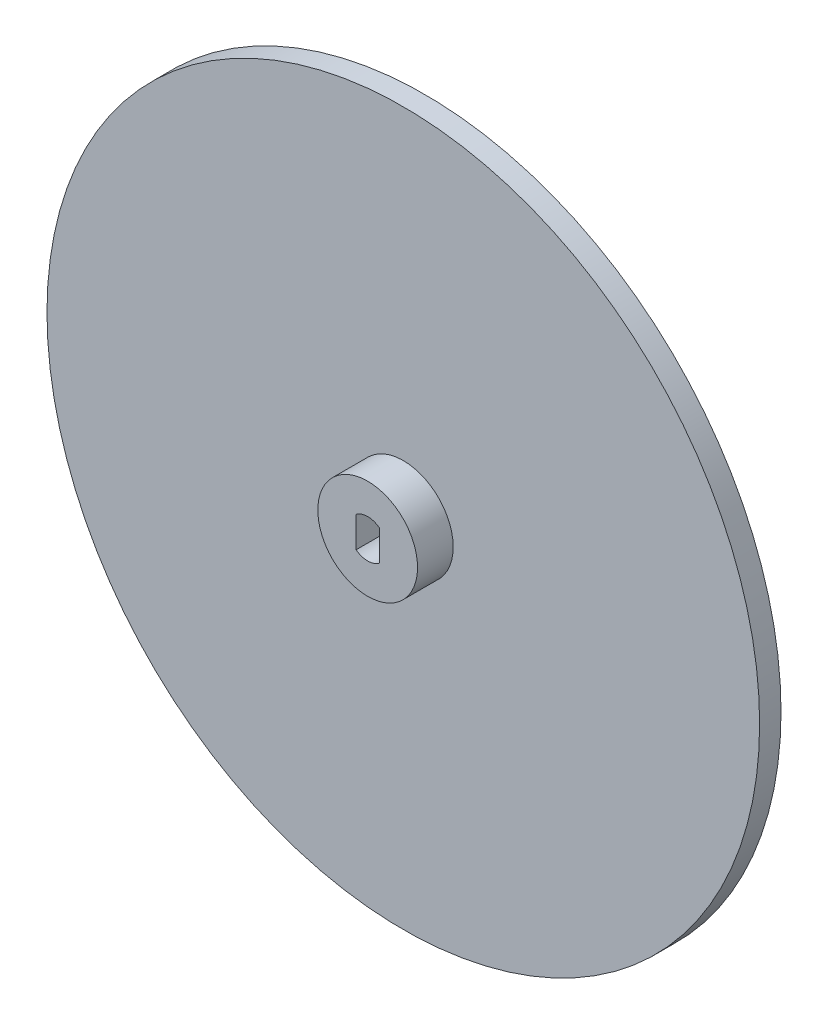
SolidWorks part; units mm, degrees
ref_plane "Front Plane" through (0, 0, 0) normal (0, 0, 1) x (1, 0, 0)
ref_plane "Top Plane" through (0, 0, 0) normal (0, 1, 0) x (1, 0, 0)
ref_plane "Right Plane" through (0, 0, 0) normal (1, 0, 0) x (0, 0, -1)
sketch "Sketch1" plane through (0, 0, 0) normal (0, 0, 1) x (1, 0, 0)
  circle A0 centre (0, 0) radius 50
  dimension "D1" = 100
extrude "Boss-Extrude1" add sketch "Sketch1" against normal blind 3
sketch "Sketch2" plane through (0, 0, 0) normal (0, 0, 1) x (1, 0, 0)
  circle A0 centre (0, 0) radius 7
  dimension "D1" = 14
extrude "Boss-Extrude2" add sketch "Sketch2" along normal blind 5
sketch "Sketch3" plane through (0, 0, 5) normal (0, 0, 1) x (1, 0, 0)
  line L0 (-1.625, 2.1562) -> (-1.625, -2.1562)
  line L1 (0, 2.7) -> (0, -2.7) construction
  line L2 (1.625, 2.1562) -> (1.625, -2.1562)
  arc A0 (-1.625, -2.1562) -> (1.625, -2.1562) centre (0, 0) ccw
  arc A1 (1.625, 2.1562) -> (-1.625, 2.1562) centre (0, 0) ccw
  dimension "D1" = 5.4
  dimension "D2" = 1.625
extrude "Cut-Extrude1" cut sketch "Sketch3" against normal blind 5
sketch "Sketch4" plane through (0, 0, -3) normal (0, 0, -1) x (-1, 0, 0)
  circle A0 centre (0, 0) radius 44.85 construction
  circle A1 centre (0, 44.85) radius 2
  dimension "D1" = 89.7
  dimension "D2" = 4
extrude "Cut-Extrude2" cut sketch "Sketch4" against normal blind 1.5
fillet "Fillet1" radius 2 1 edges at (-2, 44.85, -1.5)
pattern_circular "CirPattern4" count 16 over 360 about axis through (0, 0, 0) along (0, 0, 1) of "Cut-Extrude2", "Fillet1"
